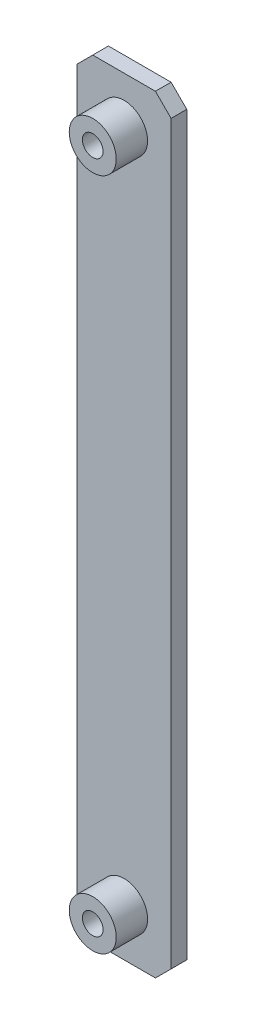
SolidWorks part; units mm, degrees
ref_plane "Front Plane" through (0, 0, 0) normal (0, 0, 1) x (1, 0, 0)
ref_plane "Top Plane" through (0, 0, 0) normal (0, 1, 0) x (1, 0, 0)
ref_plane "Right Plane" through (0, 0, 0) normal (1, 0, 0) x (0, 0, -1)
sketch "Sketch1" plane through (0, 0, 0) normal (0, 0, 1) x (1, 0, 0)
  line L1 (0, 0) -> (-9.525, 0)
  line L2 (0, 0) -> (0, 77.7875)
  line L3 (0, 77.7875) -> (-9.525, 77.7875)
  line L4 (-9.525, 0) -> (-9.525, 77.7875)
  dimension "D1" = 77.7875
  dimension "D2" = 9.525
extrude "Boss-Extrude1" add sketch "Sketch1" along normal blind 1.5875
chamfer "Chamfer2" distance 1.5875 angle 45 4 edges at (0, 77.7875, 0.7937) (-9.525, 77.7875, 0.7937) (0, 0, 0.7937) (-9.525, 0, 0.7937)
hole_wizard "#97 (0.0825) Diameter Hole1" positions "Sketch2" profile "Sketch3" hole size "#97" standard "ANSI Inch" end condition through all
sketch "Sketch2" plane through (0, 0, 1.5875) normal (0, 0, 1) x (1, 0, 0)
  line L0 (-1.5875, 77.7875) -> (-7.9375, 77.7875) construction
  line L1 (-7.9375, 0) -> (-1.5875, 0) construction
  line L2 (0, 4.7625) -> (-9.525, 4.7625) construction
  line L3 (0, 1.5875) -> (0, 76.2) construction
  line L4 (-9.525, 76.2) -> (-9.525, 1.5875) construction
  point P0 (-4.7625, 4.7625)
  point P2 (-4.7625, 73.025)
  dimension "D1" = 4.7625
  dimension "D2" = 4.7625
sketch "Sketch3" plane through (-4.7625, 4.7625, 1.5875) normal (1, 0, 0) x (0, -1, 0)
  line L0 (0, 0) -> (0, 1.5875)
  line L1 (0, 1.5875) -> (1.0477, 1.5875)
  line L2 (1.0477, 1.5875) -> (1.0477, 0)
  line L5 (1.0477, 0) -> (0, 0)
  line L11 (0, -6.35) -> (0, 107.95) construction
  dimension "Thru Hole Dia." = 2.0955
  dimension "Thru Hole Depth" = 1.5875
ref_plane "Plane1" through (0, 38.8937, 0) normal (0, 1, 0) x (1, 0, 0)
sketch "Sketch5" plane through (0, 0, 1.5875) normal (0, 0, 1) x (1, 0, 0)
  line L0 (0.8731, 38.8937) -> (-0.8731, 38.8937) construction
  circle A0 centre (-4.7625, 4.7625) radius 1.0478
  circle A1 centre (-4.7625, 4.7625) radius 2.3813
  circle A2 centre (-4.7625, 73.025) radius 2.3813
  circle A3 centre (-4.7625, 73.025) radius 1.0477
  dimension "D1" = 4.7625
  dimension "D2" = 2.0955
extrude "Boss-Extrude2" add sketch "Sketch5" along normal blind 3.175
